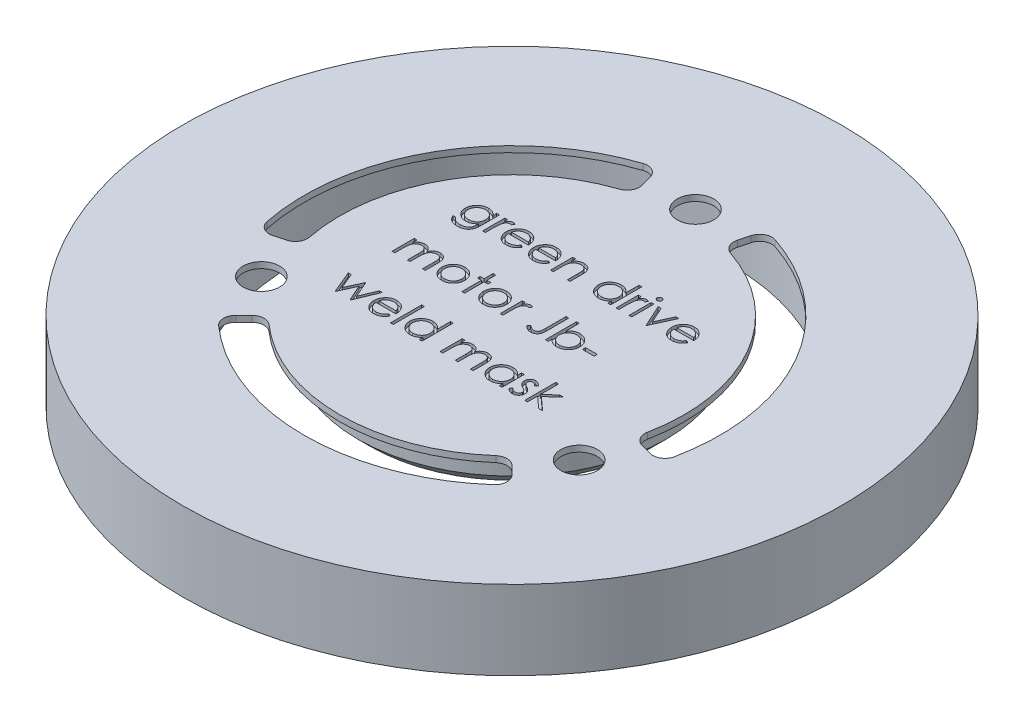
SolidWorks part; units mm, degrees
ref_plane "Front Plane" through (0, 0, 0) normal (0, 0, 1) x (1, 0, 0)
ref_plane "Top Plane" through (0, 0, 0) normal (0, 1, 0) x (1, 0, 0)
ref_plane "Right Plane" through (0, 0, 0) normal (1, 0, 0) x (0, 0, -1)
sketch "Sketch1" plane through (0, 0, 0) normal (0, 1, 0) x (1, 0, 0)
  line L0 (0, 13.075) -> (0, 17.075) construction
  line L1 (3.9126, 14.6019) -> (4.1525, 15.4972)
  line L2 (-3.9126, 14.6019) -> (-4.1525, 15.4972)
  line L3 (14.6019, -3.9126) -> (15.4972, -4.1525)
  line L4 (10.6893, -10.6893) -> (11.3447, -11.3447)
  line L5 (-10.6893, -10.6893) -> (-11.3447, -11.3447)
  line L6 (-14.6019, -3.9126) -> (-15.4972, -4.1525)
  arc A0 (-4.5565, 13.3963) -> (-13.8798, -2.7521) centre (0, 0) ccw
  arc A1 (-5.4368, 16.1863) -> (-16.7362, -3.3848) centre (0, 0) ccw
  circle A2 centre (0, 0) radius 27.075
  circle A3 centre (0, 0) radius 17.075 construction
  arc A4 (3.9126, 14.6019) -> (4.5565, 13.3963) centre (4.8785, 14.343) ccw
  arc A5 (4.1525, 15.4972) -> (5.4368, 16.1863) centre (5.1184, 15.2384) cw
  arc A6 (-4.1525, 15.4972) -> (-5.4368, 16.1863) centre (-5.1184, 15.2384) ccw
  arc A7 (-3.9126, 14.6019) -> (-4.5565, 13.3963) centre (-4.8785, 14.343) cw
  circle A8 centre (0, 15.075) radius 1.5
  arc A9 (14.6019, -3.9126) -> (13.8798, -2.7521) centre (14.8607, -2.9466) cw
  arc A10 (15.4972, -4.1525) -> (16.7362, -3.3848) centre (15.756, -3.1865) ccw
  circle A11 centre (13.0553, -7.5375) radius 1.5
  arc A12 (11.3447, -11.3447) -> (11.2994, -12.8016) centre (10.6376, -12.0518) cw
  arc A13 (10.6893, -10.6893) -> (9.3233, -10.6442) centre (9.9822, -11.3964) ccw
  arc A14 (-10.6893, -10.6893) -> (-9.3233, -10.6442) centre (-9.9822, -11.3964) cw
  arc A15 (-11.3447, -11.3447) -> (-11.2994, -12.8016) centre (-10.6376, -12.0518) ccw
  circle A16 centre (-13.0553, -7.5375) radius 1.5
  arc A17 (-15.4972, -4.1525) -> (-16.7362, -3.3848) centre (-15.756, -3.1865) cw
  arc A18 (-14.6019, -3.9126) -> (-13.8798, -2.7521) centre (-14.8607, -2.9466) ccw
  arc A19 (-11.2994, -12.8016) -> (11.2994, -12.8016) centre (0, 0) ccw
  arc A20 (-9.3233, -10.6442) -> (9.3233, -10.6442) centre (0, 0) ccw
  arc A21 (13.8798, -2.7521) -> (4.5565, 13.3963) centre (0, 0) ccw
  arc A22 (16.7362, -3.3848) -> (5.4368, 16.1863) centre (0, 0) ccw
  circle A23 centre (0, 0) radius 18.075 construction
  circle A24 centre (0, 0) radius 12.65 construction
  point P18 (4.4193, 16.4932)
  point P21 (-4.4193, 16.4932)
  point P53 (0, 13.3963)
  dimension "D1" = 28.3
  dimension "D2" = 34.15
  dimension "D5" = 1
  dimension "D6" = 3
  dimension "D8" = 36.15
  dimension "D9" = 25.3
  dimension "D4" = 15
  dimension "D10" = 4
  dimension "D3" = 10
  dimension "D7" = 3
extrude "Boss-Extrude1" add sketch "Sketch1" along normal blind 0.5
sketch "Sketch2" plane through (0, 0, 0) normal (0, -1, 0) x (1, 0, 0)
  circle A1 centre (0, 0) radius 12.65
  circle A3 centre (0, 0) radius 18.075
  circle A5 centre (0, 0) radius 27.075
  circle A6 centre (0, 0) radius 27.075 construction
  point P1 (0, 0)
  point P3 (8.5716, 9.3033)
  point P5 (13.1421, 11.9481)
  circle M10 centre (0, 0) radius 27.075
  dimension "D1" = 25.3
  dimension "D2" = 36.15
extrude "Boss-Extrude2" add sketch "Sketch2" along normal blind 3 contours A3 M10 | A1 region at (0, 0, 0) region at (-26.3092, 0, 0)
sketch "Sketch3" plane through (0, -3, 0) normal (0, -1, 0) x (1, 0, 0)
  circle A1 centre (0, 0) radius 18.075 construction
  circle A4 centre (0, 0) radius 18.075
  circle A7 centre (0, 0) radius 27.075
  circle A8 centre (0, 0) radius 27.075
  dimension "D1" = 0
extrude "Boss-Extrude3" add sketch "Sketch3" along normal blind 3
chamfer "Chamfer1" distance 1 angle 45 2 edges at (0, -3, -12.65) (0, -6, -18.075)
sketch "Sketch4" plane through (0, 0.5, 0) normal (0, 1, 0) x (1, 0, 0)
  text T0 "green drive\r\nmotor Jb-\r\nweld mask" font "Century Gothic" height 2.5
  point P1 (0, 0)
  point P2 (0, 0)
  point P3 (-9.7423, 4.8)
extrude "Cut-Extrude1" cut sketch "Sketch4" against normal blind 0.3
